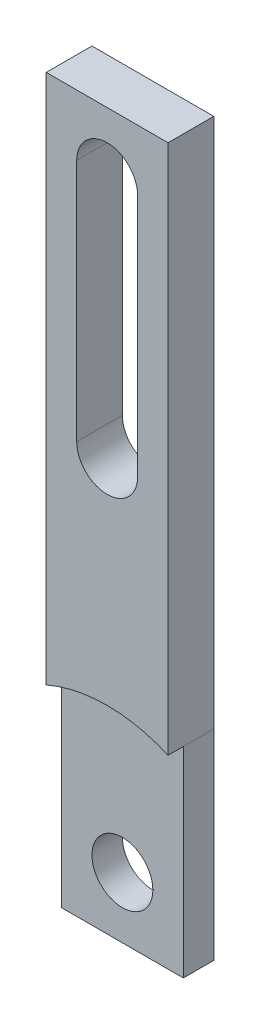
SolidWorks part; units mm, degrees
ref_plane "Plano frontal" through (0, 0, 0) normal (0, 0, 1) x (1, 0, 0)
ref_plane "Plano superior" through (0, 0, 0) normal (0, 1, 0) x (1, 0, 0)
ref_plane "Plano direito" through (0, 0, 0) normal (1, 0, 0) x (0, 0, -1)
sketch "Esboço5" plane through (0, 0, 0) normal (0, 0, 1) x (1, 0, 0)
  line L2 (-20, -86.7011) -> (20, -86.7011)
  line L3 (20, -86.7011) -> (20, -20.8754)
  line L4 (-20, -86.7011) -> (-20, -20.8754)
  arc A0 (20, -20.8754) -> (-20, -20.8754) centre (0, -66.7011) ccw
  circle A1 centre (0, -66.7011) radius 10
  dimension "D1" = 100
  dimension "D2" = 20
extrude "Ressalto-extrusão3" add sketch "Esboço5" along normal blind 5 and the other way blind 5
sketch "Esboço7" plane through (0, 0, 5) normal (0, 0, 1) x (1, 0, 0)
  line L0 (20, -20.8754) -> (20, 153.2989)
  line L1 (-20, -20.8754) -> (-20, 153.2989)
  line L2 (20, 153.2989) -> (-20, 153.2989)
  line L3 (0, 153.2989) -> (0, 86.6481) construction
  line L4 (0, 153.2989) -> (0, 143.2989)
  line L6 (-10, 133.2989) -> (-10, 53.2989)
  line L7 (10, 133.2989) -> (10, 53.2989)
  line L8 (-20, -20.8754) -> (-20, 153.2989)
  line L9 (20, 153.2989) -> (20, -20.8754)
  arc A0 (10, 133.2989) -> (-10, 133.2989) centre (0, 133.2989) ccw
  arc A1 (-10, 53.2989) -> (10, 53.2989) centre (0, 53.2989) ccw
  arc A2 (20, -20.8754) -> (-20, -20.8754) centre (0, -66.6554) ccw
  dimension "D3" = 20
  dimension "D2" = 20
  dimension "D4" = 80
extrude "Ressalto-extrusão4" add sketch "Esboço7" along normal blind 5 and the other way blind 10 separate body contours A2 L0 L2 A0 L7 A1 L6 L1 region at (0, -14.9102, 5)
